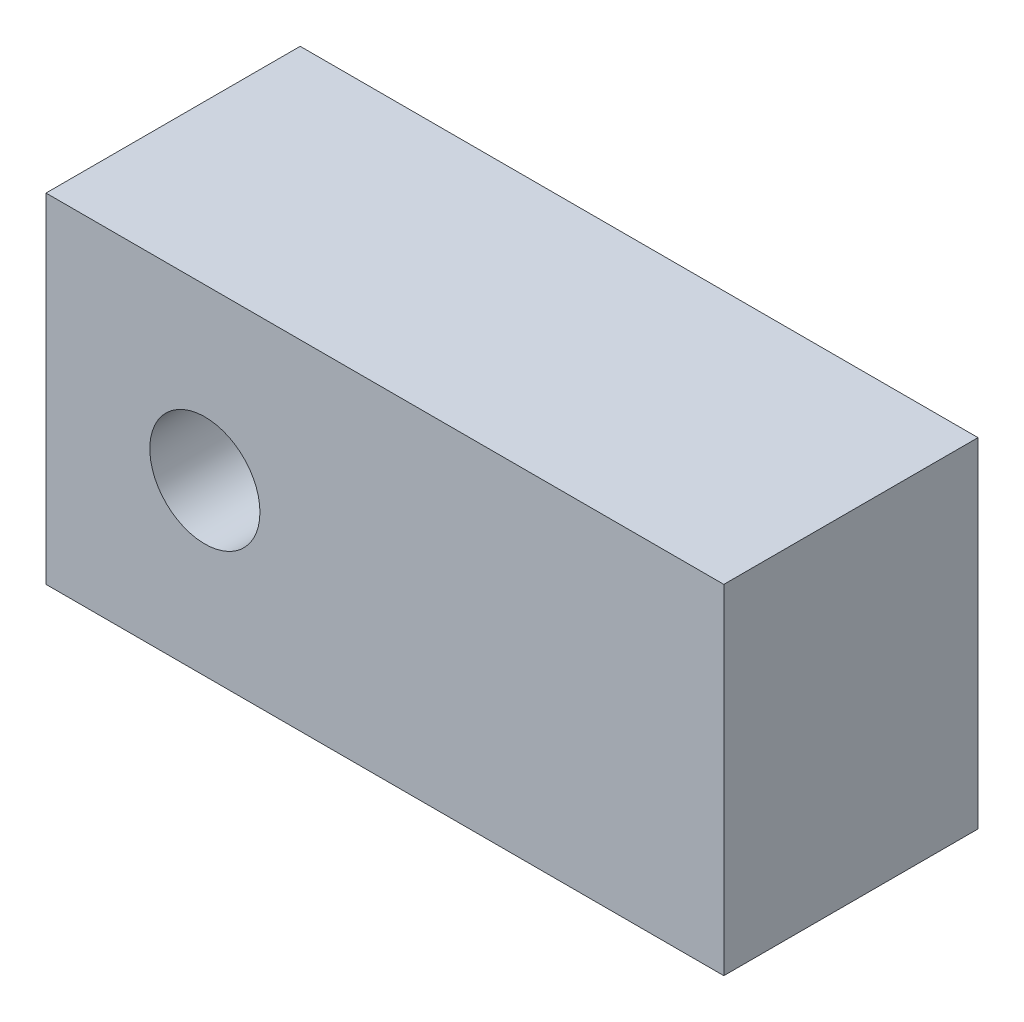
SolidWorks part; units mm, degrees
ref_plane "Front Plane" through (0, 0, 0) normal (0, 0, 1) x (1, 0, 0)
ref_plane "Top Plane" through (0, 0, 0) normal (0, 1, 0) x (1, 0, 0)
ref_plane "Right Plane" through (0, 0, 0) normal (1, 0, 0) x (0, 0, -1)
sketch "Sketch1" plane through (0, 0, 0) normal (0, 0, 1) x (1, 0, 0)
  line L1 (0, 0) -> (20.32, 0)
  line L2 (0, 0) -> (0, 10.16)
  line L3 (0, 10.16) -> (20.32, 10.16)
  line L4 (20.32, 0) -> (20.32, 10.16)
  line L5 (0, 0) -> (20.32, 10.16) construction
  line L6 (0, 10.16) -> (20.32, 0) construction
  point P4 (10.16, 5.08)
  dimension "D1" = 20.32
  dimension "D2" = 10.16
extrude "Boss-Extrude1" add sketch "Sketch1" along normal blind 7.62
sketch "Sketch2" plane through (0, 0, 7.62) normal (0, 0, 1) x (1, 0, 0)
  line L0 (0, 10.16) -> (0, 0) construction
  circle A0 centre (4.7625, 5.08) radius 1.651
  point P5 (0, 5.08)
  dimension "D1" = 3.302
  dimension "D2" = 4.7625
extrude "Cut-Extrude1" cut sketch "Sketch2" against normal through all
